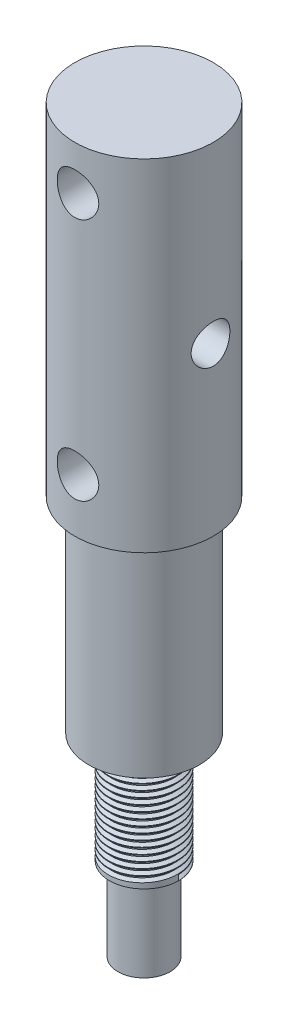
SolidWorks part; units mm, degrees
material "AISI 316 Annealed Stainless Steel Bar (SS)"
ref_plane "Front Plane" through (0, 0, 0) normal (0, 0, 1) x (1, 0, 0)
ref_plane "Top Plane" through (0, 0, 0) normal (0, 1, 0) x (1, 0, 0)
ref_plane "Right Plane" through (0, 0, 0) normal (1, 0, 0) x (0, 0, -1)
sketch "Sketch2" plane through (0, 0, 0) normal (0, 0, 1) x (1, 0, 0)
  line L0 (0, 0) -> (0, 508.8276) construction
  line L1 (0, 0) -> (6, 0)
  line L2 (0, 0) -> (0, 19.05)
  line L3 (0, 19.05) -> (6, 19.05)
  line L4 (6, 0) -> (6, 19.05)
  line L5 (0, 19.05) -> (7.9375, 19.05)
  line L6 (0, 19.05) -> (0, 44.45)
  line L7 (0, 44.45) -> (7.9375, 44.45)
  line L8 (7.9375, 19.05) -> (7.9375, 44.45)
  line L9 (0, 44.45) -> (12.721, 44.45)
  line L10 (0, 44.45) -> (0, 91.44)
  line L11 (0, 91.44) -> (12.721, 91.44)
  line L12 (12.721, 44.45) -> (12.721, 91.44)
  line L13 (0, 91.44) -> (15.875, 91.44)
  line L14 (0, 91.44) -> (0, 169.672)
  line L15 (0, 169.672) -> (15.875, 169.672)
  line L16 (15.875, 91.44) -> (15.875, 169.672)
  dimension "D1" = 78.232
  dimension "D2" = 15.875
  dimension "D4" = 46.99
  dimension "D3" = 12.721
  dimension "D5" = 25.4
  dimension "D6" = 7.9375
  dimension "D7" = 19.05
  dimension "D8" = 6
revolve "Revolve1" add sketch "Sketch2" angle 360 about L0 region at (3, 9.525, 0) region at (3.9687, 31.75, 0) region at (6.3605, 67.945, 0) region at (7.9375, 130.556, 0)
thread "Thread2" pitch 1.4111 method cut profile "Thread Profile3" start angle 0, offset 0, length 0, pitch 1.4111, diameter 15.875
ref_plane "Plane3" through (7.9375, 19.05, 0) normal (0, 0, 1) x (1, 0, 0)
sketch "Thread Profile3" plane through (7.9375, 19.05, 0) normal (0, 0, 1) x (1, 0, 0)
  line L0 (0, 0) -> (0, 1.4111) construction
  line L11 (0, 0) -> (0, 1.2347)
  line L12 (0, 1.2347) -> (-0.7638, 0.7937)
  line L13 (-0.7638, 0.7937) -> (-0.7638, 0.441)
  line L15 (-0.7638, 0.441) -> (0, 0)
  line L17 (-0.7638, 0.6174) -> (0, 0.6174) construction
  point P2 (0, 0)
  dimension "Pitch" = 1.4111
  dimension "Profile_Angle" = 60
  dimension "Profile_Land" = 0.3528
  dimension "Profile_Height" = 0.7638
sketch "Sketch3" plane through (0, 0, 0) normal (0, 0, 1) x (1, 0, 0)
  line L0 (0, 0) -> (0, 197.3408) construction
  line L1 (15.875, 169.672) -> (-15.875, 169.672) construction
  circle A0 centre (0, 159.512) radius 4.7625
  circle A1 centre (0, 103.632) radius 4.7625
  dimension "D1" = 9.525
  dimension "D2" = 10.16
  dimension "D3" = 66.04
extrude "Cut-Extrude1" cut sketch "Sketch3" against normal through all both and the other way through all
sketch "Sketch6" plane through (0, 0, 0) normal (1, 0, 0) x (0, 0, -1)
  line L0 (15.875, 169.672) -> (-15.875, 169.672) construction
  circle A0 centre (0, 129.667) radius 4.445
  dimension "D2" = 8.89
  dimension "D1" = 40.005
extrude "Cut-Extrude2" cut sketch "Sketch6" against normal through all both and the other way through all
sketch "Sketch9" plane through (0, 0, 0) normal (1, 0, 0) x (0, 0, -1)
  line L0 (15.875, 169.672) -> (-15.875, 169.672) construction
  circle A0 centre (0, 163.322) radius 3.175
  circle A1 centre (0, 150.622) radius 3.175
  point P0 (0, 163.322)
  point P1 (0, 150.622)
  dimension "D3" = 6.35
  dimension "D4" = 6.35
  dimension "D1" = 6.35
  dimension "D2" = 12.7
equation "\"hole diamiter\"= 1.25in"
equation "\"wheel depth\"= 2.88"
equation "\"press_tolerance\"= 0.00165"
equation "\"wheel_connection\"= \"hole diamiter\"'https://at-machining.com/tolerance-press-fit/"
equation "\"D1@Sketch2\"=\"wheel depth\"+0.2"
equation "\"D2@Sketch2\"=\"wheel_connection\"/2"
equation "\"fitting depth\"= 1.85"
equation "\"D4@Sketch2\"=\"fitting depth\""
equation "\"bearing_id\"= 1"
equation "\"bearing_connection\"= \"bearing_id\" + \"press_tolerance\"'https://at-machining.com/tolerance-press-fit/"
equation "\"D3@Sketch2\"=\"bearing_connection\"/2"
equation "\"thread length\"= 1"
equation "\"major_diamiter\"= 5 / 8'https://www.machiningdoctor.com/threadinfo/?tid=81"
equation "\"D5@Sketch2\"=\"thread length\""
equation "\"D6@Sketch2\"=\"major_diamiter\"/2"
equation "\"coupling diamiter\"= 12mm"
equation "\"coupling lenght\"= 1.5 / 2"
equation "\"D7@Sketch2\"=\"coupling lenght\""
equation "\"D8@Sketch2\"=\"coupling diamiter\"/2"
equation "\"hub_spacing\"= .5"
equation "\"D2@Sketch9\"=\"hub_spacing\""
